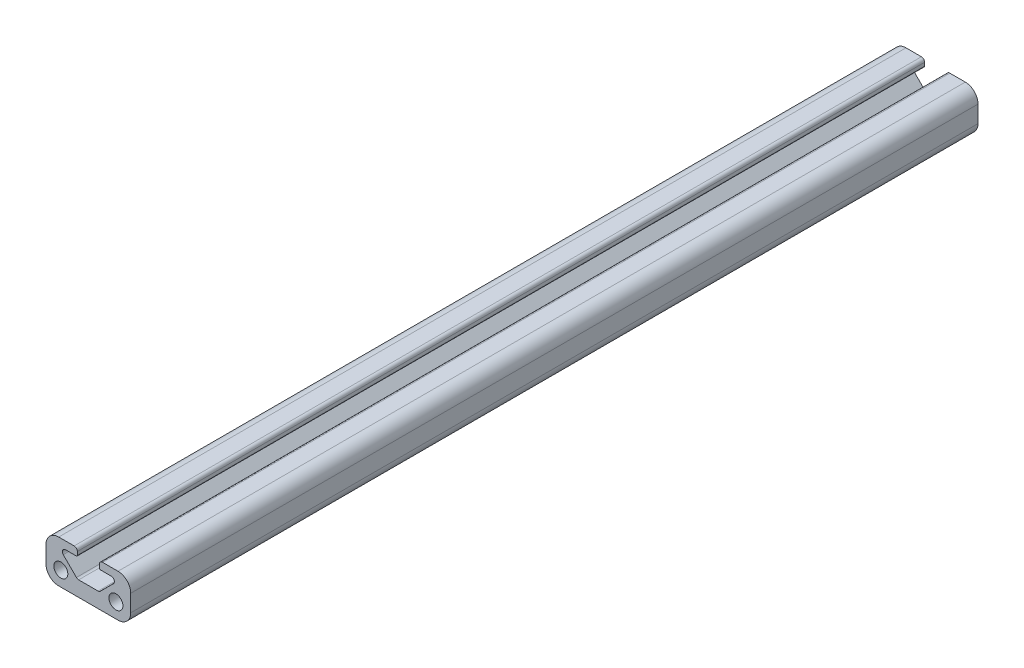
SolidWorks part; units mm, degrees
material "6063-T6"
ref_plane "Front Plane" through (0, 0, 0) normal (0, 0, 1) x (1, 0, 0)
ref_plane "Top Plane" through (0, 0, 0) normal (0, 1, 0) x (1, 0, 0)
ref_plane "Right Plane" through (0, 0, 0) normal (1, 0, 0) x (0, 0, -1)
sketch "Sketch1" plane through (0, 0, 0) normal (0, 0, 1) x (1, 0, 0)
  line L0 (-7, 10) -> (-3.35, 10)
  line L2 (-10, 7) -> (-10, 3)
  line L3 (-7, 0) -> (7, 0)
  line L4 (10, 7) -> (10, 3)
  line L5 (-2.6, 9.25) -> (-2.6, 8.45)
  line L6 (-2.85, 8.2) -> (-5.3893, 8.2)
  line L7 (-5.9197, 6.9197) -> (-2.8197, 3.8197)
  line L8 (-2.2893, 3.6) -> (2.2893, 3.6)
  line L9 (2.8197, 3.8197) -> (5.9197, 6.9197)
  line L10 (5.3893, 8.2) -> (2.85, 8.2)
  line L11 (2.6, 8.45) -> (2.6, 9.25)
  line L12 (3.35, 10) -> (7, 10)
  line L13 (0, -55) -> (0, 55) construction
  line L14 (6.5, 3.5) -> (-6.5, 3.5) construction
  arc A0 (7, 10) -> (10, 7) centre (7, 7) cw
  arc A1 (7, 0) -> (10, 3) centre (7, 3) ccw
  arc A2 (-10, 3) -> (-7, 0) centre (-7, 3) ccw
  arc A3 (-7, 10) -> (-10, 7) centre (-7, 7) ccw
  arc A4 (2.2893, 3.6) -> (2.8197, 3.8197) centre (2.2893, 4.35) ccw
  arc A5 (-2.8197, 3.8197) -> (-2.2893, 3.6) centre (-2.2893, 4.35) ccw
  arc A6 (5.9197, 6.9197) -> (5.3893, 8.2) centre (5.3893, 7.45) ccw
  arc A7 (-5.3893, 8.2) -> (-5.9197, 6.9197) centre (-5.3893, 7.45) ccw
  arc A8 (2.6, 9.25) -> (3.35, 10) centre (3.35, 9.25) cw
  arc A9 (-3.35, 10) -> (-2.6, 9.25) centre (-3.35, 9.25) cw
  arc A10 (2.85, 8.2) -> (2.6, 8.45) centre (2.85, 8.45) cw
  arc A11 (-2.6, 8.45) -> (-2.85, 8.2) centre (-2.85, 8.45) cw
  circle A12 centre (-6.5, 3.5) radius 1.65
  circle A13 centre (6.5, 3.5) radius 1.65
  point P4 (0, 3.6)
  point P18 (0, 3.5)
  point P25 (10, 0)
  point P28 (-10, 0)
  point P31 (-10, 10)
  point P36 (-2.6, 3.6)
  dimension "D6" = 3
  dimension "D7" = 0.75
  dimension "D8" = 0.25
  dimension "D11" = 3.3
  dimension "D1" = 20
  dimension "D2" = 10
  dimension "D3" = 6.4
  dimension "D4" = 5.2
  dimension "D5" = 4.6
  dimension "D9" = 3.5
  dimension "D10" = 13
extrude "Boss-Extrude1" add sketch "Sketch1" along normal mid plane 200
hole_wizard "M5 Clearance Hole1" positions "Sketch2" profile "Sketch3" hole size "M5" standard "ANSI Metric" end condition through all
sketch "Sketch2" plane through (0, 0, 0) normal (0, -1, 0) x (-1, 0, 0)
  line L0 (0, -40) -> (0, 40)
  point P0 (0, 40)
  point P2 (0, -40)
  dimension "D1" = 80
sketch "Sketch3" plane through (0, 0, -40) normal (1, 0, 0) x (0, 0, -1)
  line L0 (0, 0) -> (0, 10)
  line L1 (0, 10) -> (2.6, 10)
  line L2 (2.6, 10) -> (2.6, 0)
  line L5 (2.6, 0) -> (0, 0)
  line L11 (0, -6.35) -> (0, 107.95) construction
  dimension "Thru Hole Dia." = 5.2
  dimension "Thru Hole Depth" = 10
